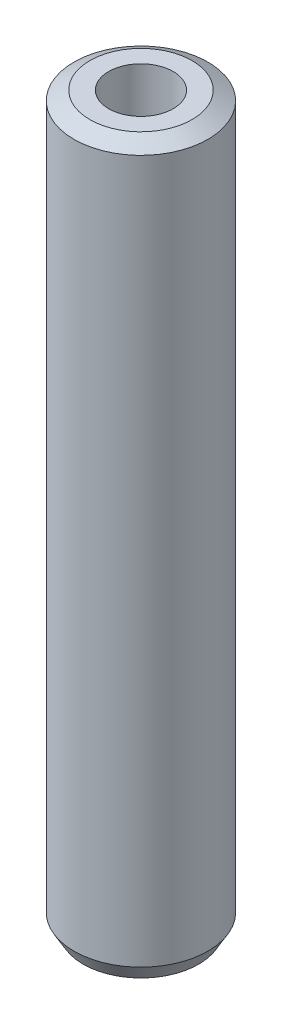
SolidWorks part; units mm, degrees
ref_plane "Front Plane" through (0, 0, 0) normal (0, 0, 1) x (1, 0, 0)
ref_plane "Top Plane" through (0, 0, 0) normal (0, 1, 0) x (1, 0, 0)
ref_plane "Right Plane" through (0, 0, 0) normal (1, 0, 0) x (0, 0, -1)
sketch "Sketch1" plane through (0, 0, 0) normal (0, 1, 0) x (1, 0, 0)
  circle A0 centre (0, 0) radius 35
  dimension "SHAFT_OD" = 70
extrude "Boss-Extrude1" add sketch "Sketch1" along normal blind 380.4577
sketch "Sketch2" plane through (0, 0, 0) normal (0, 1, 0) x (1, 0, 0)
  circle A0 centre (0, 0) radius 16.8604
  dimension "BORE_D" = 33.7208
extrude "Cut-Extrude1" cut sketch "Sketch2" along normal through all
chamfer "Chamfer1" distance 4.7882 angle 60 2 edges at (0, 380.4577, 35) (0, 0, 35) first distance on face at (0, 380.4577, 35) first distance on face at (0, 0, 16.8604)
